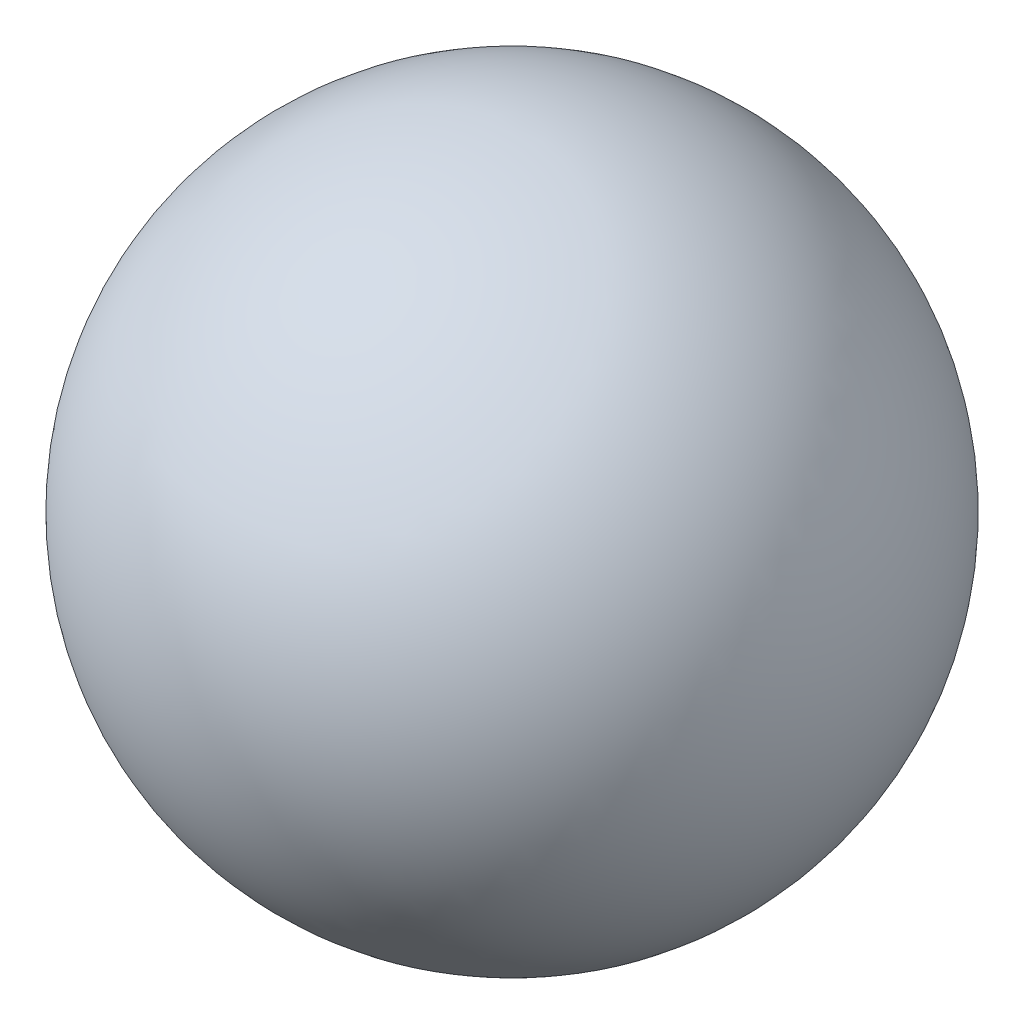
SolidWorks part; units mm, degrees
ref_plane "Front Plane" through (0, 0, 0) normal (0, 0, 1) x (1, 0, 0)
ref_plane "Top Plane" through (0, 0, 0) normal (0, 1, 0) x (1, 0, 0)
ref_plane "Right Plane" through (0, 0, 0) normal (1, 0, 0) x (0, 0, -1)
sketch "Sketch1" plane through (0, 0, 0) normal (0, 0, 1) x (1, 0, 0)
  line L0 (0, 4.7625) -> (0, -4.7625) construction
  line L1 (0, 4.7625) -> (0, -4.7625)
  arc A0 (0, 4.7625) -> (0, -4.7625) centre (0, 0) ccw
  dimension "D1" = 9.525
revolve "Revolve3" add sketch "Sketch1" angle 360 about L0
ref_axis "Axis1" through (5.2388, 0, 0) along (-1, 0, 0)
